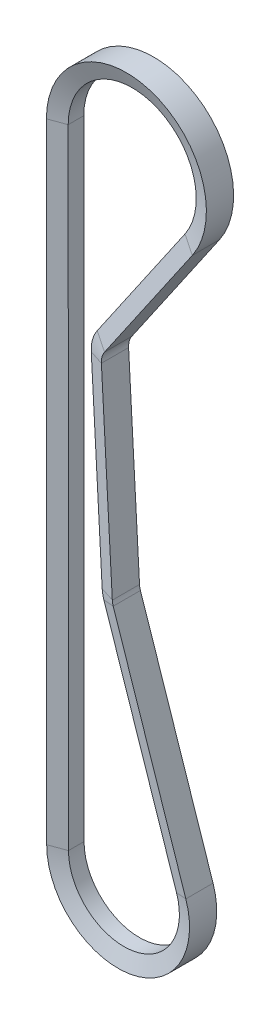
SolidWorks part; units mm, degrees
ref_plane "Front Plane" through (0, 0, 0) normal (0, 0, 1) x (1, 0, 0)
ref_plane "Top Plane" through (0, 0, 0) normal (0, 1, 0) x (1, 0, 0)
ref_plane "Right Plane" through (0, 0, 0) normal (1, 0, 0) x (0, 0, -1)
sketch "Sketch2" plane through (0, 0, 0) normal (0, 0, 1) x (1, 0, 0)
  line L0 (0, 0) -> (1, 0) construction
  line L1 (0, 0) -> (0, 1) construction
  line L12 (-25, -0.011) -> (-25.0965, 219.9686)
  line L14 (25.9747, 204.1152) -> (-4.7447, 159.4442)
  line L15 (-5.853, 155.4993) -> (-2.0292, 85.6038)
  line L16 (-1.7108, 83.9366) -> (23.7092, 7.9293)
  arc A4 (-25.0965, 219.9686) -> (25.9747, 204.1152) centre (2.9035, 219.9808) cw
  arc A7 (23.7092, 7.9293) -> (-25, -0.011) centre (0, 0) cw
  arc A8 (-4.7447, 159.4442) -> (-5.853, 155.4993) centre (0.4875, 155.8461) ccw
  arc A9 (-2.0292, 85.6038) -> (-1.7108, 83.9366) centre (4.3113, 85.9507) ccw
ref_plane "Plane4" through (23.7092, 7.9293, 0) normal (0.3172, -0.9484, 0) x (-0.9484, -0.3172, 0)
sketch "Sketch3" plane through (23.7092, 7.9293, 0) normal (0.3172, -0.9484, 0) x (-0.9484, -0.3172, 0)
  line L0 (0, -4.7625) -> (0, 4.7625)
  line L1 (0, -4.7625) -> (5.588, -2.7286)
  line L2 (5.588, -2.7286) -> (5.588, 2.7286)
  line L3 (5.588, 2.7286) -> (0, 4.7625)
  line L4 (0, 0) -> (5.588, 0) construction
  dimension "D1" = 9.525
  dimension "D2" = 5.588
  dimension "D3" = 40
sweep "Sweep1" add profiles "Sketch3" path "Sketch2"
